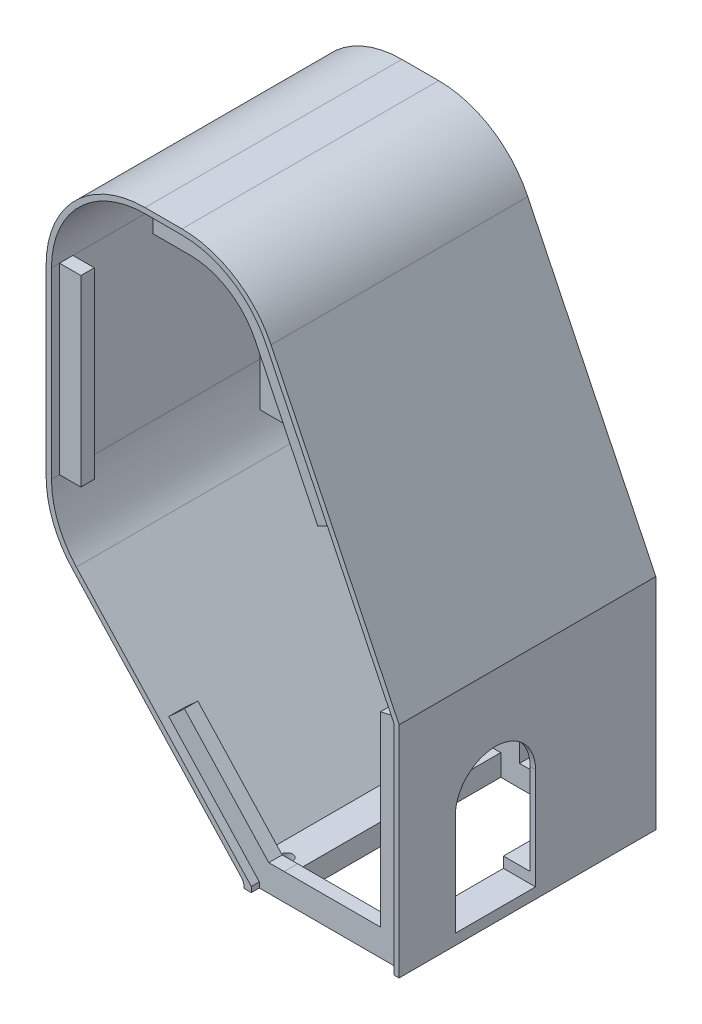
SolidWorks part; units mm, degrees
ref_plane "정면" through (0, 0, 0) normal (0, 0, 1) x (1, 0, 0)
ref_plane "윗면" through (0, 0, 0) normal (0, 1, 0) x (1, 0, 0)
ref_plane "우측면" through (0, 0, 0) normal (1, 0, 0) x (0, 0, -1)
sketch "스케치1" plane through (0, 0, 0) normal (0, 0, 1) x (1, 0, 0)
  line L0 (-65.9497, 38.7926) -> (-28.9497, -1.2074)
  line L1 (-28.9497, 98.7926) -> (-65.9497, 98.7926)
  line L2 (-65.9497, 38.7926) -> (-65.9497, 98.7926)
  line L4 (-28.9497, 98.7926) -> (0.0503, 38.7926)
  line L5 (0.0503, 38.7926) -> (0.0503, -1.2074)
  line L9 (-28.9497, -1.2074) -> (-28.9497, -2.2074)
  line L10 (-28.9497, -2.2074) -> (0.0503, -2.2074)
  line L11 (0.0503, -1.2074) -> (0.0503, -2.2074)
  line L12 (-28.9497, -1.2074) -> (0.0503, -2.2074) construction
  line L13 (-28.9497, -2.2074) -> (0.0503, -1.2074) construction
  point P10 (-14.4497, -1.7074)
  dimension "D1" = 37
  dimension "D2" = 29
  dimension "D3" = 40
  dimension "D5" = 1
extrude "보스-돌출1" add sketch "스케치1" against normal blind 6
fillet "필렛1" radius 18.5 3 edges at (-28.9497, 98.7926, -3) (-65.9497, 98.7926, -3) (-65.9497, 38.7926, -3)
sketch "스케치3" plane through (0, 0, -6) normal (0, 0, -1) x (-1, 0, 0)
  circle A0 centre (47.4497, 80.2926) radius 16.15
  dimension "D1" = 32.3
extrude "컷-돌출1" cut sketch "스케치3" against normal blind 4.5
sketch "스케치4" plane through (0, 0, -1.5) normal (0, 0, -1) x (-1, 0, 0)
  circle A0 centre (47.4497, 80.2926) radius 14.85
  circle A1 centre (47.4497, 80.2926) radius 16.15 construction
  dimension "D1" = 1.3
extrude "컷-돌출2" cut sketch "스케치4" against normal up to next
chamfer "모따기1" distance 1 angle 67 1 edges at (-63.5997, 80.2926, -6)
sketch "스케치5" plane through (0, 0, 0) normal (0, 0, 1) x (1, 0, 0)
  line L1 (-61.4497, 47.2926) -> (-33.4497, 47.2926)
  line L2 (-61.4497, 47.2926) -> (-61.4497, 41.2926)
  line L3 (-61.4497, 41.2926) -> (-33.4497, 41.2926)
  line L4 (-33.4497, 47.2926) -> (-33.4497, 41.2926)
  line L5 (-61.4497, 47.2926) -> (-33.4497, 41.2926) construction
  line L6 (-61.4497, 41.2926) -> (-33.4497, 47.2926) construction
  line L7 (-61.4497, 67.2926) -> (-58.4041, 67.2926)
  line L8 (-61.4497, 67.2926) -> (-61.4497, 57.2926)
  line L9 (-61.4497, 57.2926) -> (-54.5997, 57.2926)
  line L10 (-54.5997, 64.8693) -> (-54.5997, 57.2926)
  line L11 (-61.4497, 67.2926) -> (-54.5997, 57.2926) construction
  line L13 (-33.4497, 67.2926) -> (-36.4952, 67.2926)
  line L14 (-33.4497, 67.2926) -> (-33.4497, 57.2926)
  line L15 (-33.4497, 57.2926) -> (-40.2997, 57.2926)
  line L16 (-40.2997, 64.8693) -> (-40.2997, 57.2926)
  line L17 (-33.4497, 67.2926) -> (-40.2997, 57.2926) construction
  circle A0 centre (-47.4497, 80.2926) radius 14.85 construction
  arc A1 (-58.4041, 67.2926) -> (-54.5997, 64.8693) centre (-47.4497, 80.2926) ccw
  arc A2 (-40.2997, 64.8693) -> (-36.4952, 67.2926) centre (-47.4497, 80.2926) ccw
  point P4 (-47.4497, 44.2926)
  dimension "D3" = 33
  dimension "D6" = 14
  dimension "D9" = 34
  dimension "D1" = 6
  dimension "D2" = 10
  dimension "D4" = 10
  dimension "D5" = 10
  dimension "D7" = 28
  dimension "D8" = 14.3
extrude "보스-돌출2" add sketch "스케치5" along normal blind 6.5
sketch "스케치6" plane through (0, 0, 6.5) normal (0, 0, 1) x (1, 0, 0)
  line L0 (-33.4497, 47.2926) -> (-61.4497, 47.2926) construction
  line L1 (-54.5997, 47.2926) -> (-40.2997, 47.2926)
  line L2 (-54.5997, 47.2926) -> (-54.5997, 44.4926)
  line L3 (-54.5997, 44.4926) -> (-40.2997, 44.4926)
  line L4 (-40.2997, 47.2926) -> (-40.2997, 44.4926)
  line L5 (-54.5997, 47.2926) -> (-40.2997, 44.4926) construction
  line L6 (-54.5997, 44.4926) -> (-40.2997, 47.2926) construction
  line L7 (-61.4497, 41.2926) -> (-33.4497, 41.2926) construction
  point P4 (-47.4497, 45.8926)
  point P9 (-54.5997, 45.8926)
  point P10 (-47.4497, 41.2926)
  dimension "D1" = 3.2
  dimension "D2" = 14.3
  dimension "D3" = 7.15
extrude "컷-돌출3" cut sketch "스케치6" against normal blind 1.5
sketch "스케치7" plane through (0, 47.2926, 0) normal (0, 1, 0) x (1, 0, 0)
  line L0 (-54.5997, -5) -> (-54.5997, -6.5) construction
  line L1 (-61.4497, -6.5) -> (-54.5997, -6.5)
  line L2 (-61.4497, -6.5) -> (-61.4497, -3.5)
  line L3 (-61.4497, -3.5) -> (-54.5997, -3.5)
  line L4 (-54.5997, -6.5) -> (-54.5997, -3.5)
  line L5 (-61.4497, -6.5) -> (-54.5997, -3.5) construction
  line L6 (-61.4497, -3.5) -> (-54.5997, -6.5) construction
  line L7 (-33.4497, -6.5) -> (-40.2997, -6.5)
  line L8 (-33.4497, -6.5) -> (-33.4497, -3.8442)
  line L9 (-33.4497, -3.8442) -> (-40.2997, -3.8442)
  line L10 (-40.2997, -6.5) -> (-40.2997, -3.8442)
  line L11 (-33.4497, -6.5) -> (-40.2997, -3.8442) construction
  line L12 (-33.4497, -3.8442) -> (-40.2997, -6.5) construction
  line L14 (-40.2997, -5) -> (-40.2997, -6.5) construction
  point P4 (-58.0247, -5)
  point P10 (-36.8747, -5.1721)
  dimension "D1" = 3
extrude "보스-돌출3" add sketch "스케치7" along normal blind 28
sketch "스케치8" plane through (0, 0, 6.5) normal (0, 0, 1) x (1, 0, 0)
  line L0 (-54.5997, 44.4926) -> (-40.2997, 44.4926) construction
  line L1 (-57.6997, 71.7926) -> (-37.1997, 71.7926) construction
  line L2 (-57.6997, 71.7926) -> (-57.6997, 51.2926) construction
  line L3 (-57.6997, 51.2926) -> (-37.1997, 51.2926) construction
  line L4 (-37.1997, 71.7926) -> (-37.1997, 51.2926) construction
  line L5 (-57.6997, 71.7926) -> (-37.1997, 51.2926) construction
  line L6 (-57.6997, 51.2926) -> (-37.1997, 71.7926) construction
  circle A0 centre (-57.6997, 71.7926) radius 1.15
  circle A1 centre (-37.1997, 71.7926) radius 1.15
  circle A2 centre (-37.1997, 51.2926) radius 1.15
  circle A3 centre (-57.6997, 51.2926) radius 1.15
  circle A4 centre (-47.4497, 80.2926) radius 14.85 construction
  point P4 (-47.4497, 61.5426)
  dimension "D1" = 2.3
  dimension "D4" = 10.25
  dimension "D2" = 20.5
  dimension "D3" = 6.8
extrude "컷-돌출4" cut sketch "스케치8" against normal up to next
sketch "스케치9" plane through (0, 0, -6) normal (0, 0, -1) x (-1, 0, 0)
  circle A0 centre (57.6997, 51.2926) radius 2.1
  circle A1 centre (37.1997, 51.2926) radius 2.1
  dimension "D1" = 4.2
extrude "컷-돌출5" cut sketch "스케치9" against normal up to next
sketch "스케치10" plane through (0, 0, 6.5) normal (0, 0, 1) x (1, 0, 0)
  circle A0 centre (-47.4497, 80.2926) radius 10.75
  dimension "D1" = 21.5
extrude "컷-돌출6" cut sketch "스케치10" against normal up to next
sketch "스케치11" plane through (0, 0, -6) normal (0, 0, -1) x (-1, 0, 0)
  line L0 (26.9497, -2.2074) -> (26.9497, 36.7926) construction
  line L1 (28.9497, -2.2074) -> (-0.0503, -2.2074) construction
  line L2 (26.9497, 36.7926) -> (9.9497, 36.7926) construction
  line L3 (-0.0503, -2.2074) -> (-0.0503, 38.7926) construction
  line L4 (28.9497, -1.2074) -> (28.9497, -2.2074) construction
  line L5 (26.9497, 36.7926) -> (54.9497, 36.7926) construction
  circle A0 centre (9.9497, 36.7926) radius 1.4
  circle A1 centre (26.9497, 26.7926) radius 1.4
  circle A2 centre (26.9497, 6.7926) radius 1.4
  circle A3 centre (54.9497, 36.7926) radius 1.4
  dimension "D1" = 2.8
  dimension "D2" = 20
  dimension "D3" = 10
  dimension "D4" = 10
  dimension "D7" = 45
  dimension "D5" = 2
  dimension "D6" = 2
extrude "컷-돌출7" cut sketch "스케치11" against normal up to next
sketch "스케치12" plane through (0, 0, 0) normal (0, 0, 1) x (1, 0, 0)
  line L22 (0.0503, -2.2074) -> (0.0503, 38.7926) construction
  line L26 (-0.9497, -2.2074) -> (-0.9497, 38.5636)
  line L27 (-60.2964, 34.1536) -> (-28.2156, -0.5284)
  line L28 (-64.9497, 80.2926) -> (-64.9497, 46.0368)
  line L29 (-40.5556, 97.7926) -> (-47.4497, 97.7926)
  line L30 (-0.9497, 38.5636) -> (-24.7995, 87.908)
  line L31 (-0.9497, -2.2074) -> (-0.9497, 38.5636)
  line L32 (-60.2964, 34.1536) -> (-27.5875, -1.2074)
  line L33 (-64.9497, 80.2926) -> (-64.9497, 46.0368)
  line L34 (-40.5556, 97.7926) -> (-47.4497, 97.7926)
  line L35 (-0.9497, 38.5636) -> (-24.7995, 87.908)
  line L59 (-27.5875, -1.2074) -> (-27.5875, -2.2074)
  line L61 (-28.9497, -1.2074) -> (-28.9497, -2.2074)
  line L62 (-28.9497, -2.2074) -> (-27.5875, -2.2074)
  line L63 (-40.5556, 98.7926) -> (-47.4497, 98.7926)
  line L64 (0.0503, -2.2074) -> (0.0503, 38.7926)
  line L65 (0.0503, 38.7926) -> (-23.8992, 88.3432)
  line L66 (-61.0305, 33.4746) -> (-28.9497, -1.2074)
  line L67 (-65.9497, 80.2926) -> (-65.9497, 46.0368)
  line L68 (-40.5556, 98.7926) -> (-47.4497, 98.7926)
  line L69 (0.0503, -1.2074) -> (0.0503, 38.7926)
  line L70 (0.0503, 38.7926) -> (-23.8992, 88.3432)
  line L71 (-61.0305, 33.4746) -> (-28.9497, -1.2074)
  line L72 (-65.9497, 80.2926) -> (-65.9497, 46.0368)
  line L73 (0.0503, -1.2074) -> (0.0503, -2.2074)
  line L74 (-28.9497, -1.2074) -> (0.0503, -2.2074) construction
  line L75 (-28.9497, -2.2074) -> (0.0503, -1.2074) construction
  line L77 (-0.9497, -2.2074) -> (0.0503, -2.2074)
  arc A18 (-64.9497, 46.0368) -> (-60.2964, 34.1536) centre (-47.4497, 46.0368) ccw
  arc A19 (-47.4497, 97.7926) -> (-64.9497, 80.2926) centre (-47.4497, 80.2926) ccw
  arc A20 (-24.7995, 87.908) -> (-40.5556, 97.7926) centre (-40.5556, 80.2926) ccw
  arc A21 (-64.9497, 46.0368) -> (-60.2964, 34.1536) centre (-47.4497, 46.0368) ccw
  arc A22 (-47.4497, 97.7926) -> (-64.9497, 80.2926) centre (-47.4497, 80.2926) ccw
  arc A23 (-24.7995, 87.908) -> (-40.5556, 97.7926) centre (-40.5556, 80.2926) ccw
  arc A41 (-23.8992, 88.3432) -> (-40.5556, 98.7926) centre (-40.5556, 80.2926) ccw
  arc A42 (-65.9497, 46.0368) -> (-61.0305, 33.4746) centre (-47.4497, 46.0368) ccw
  arc A43 (-47.4497, 98.7926) -> (-65.9497, 80.2926) centre (-47.4497, 80.2926) ccw
  arc A44 (-23.8992, 88.3432) -> (-40.5556, 98.7926) centre (-40.5556, 80.2926) ccw
  arc A45 (-65.9497, 46.0368) -> (-61.0305, 33.4746) centre (-47.4497, 46.0368) ccw
  arc A46 (-47.4497, 98.7926) -> (-65.9497, 80.2926) centre (-47.4497, 80.2926) ccw
  point P8 (-14.4497, -1.7074)
  dimension "D1" = 1
  dimension "D2" = 0
extrude "보스-돌출4" add sketch "스케치12" along normal blind 42
sketch "스케치13" plane through (0, -2.2074, 0) normal (0, -1, 0) x (1, 0, 0)
  line L0 (-28.9497, -3) -> (0.0503, -3) construction
  line L2 (-28.9497, -6) -> (-28.9497, 42) construction
  line L3 (-28.9497, -6) -> (0.0503, -6) construction
  line L4 (0.0503, -6) -> (0.0503, 42) construction
  circle A1 centre (-14.4497, -3) radius 1.1
  dimension "D1" = 14.5
  dimension "D4" = 3
extrude "컷-돌출8" cut sketch "스케치13" against normal blind 8
sketch "스케치14" plane through (0, -2.2074, 0) normal (0, -1, 0) x (1, 0, 0)
  line L1 (-28.9497, -6) -> (-22.9497, -6)
  line L2 (-28.9497, -6) -> (-28.9497, 40)
  line L3 (-28.9497, 40) -> (-22.9497, 40)
  line L4 (-22.9497, -6) -> (-22.9497, 40)
  line L5 (-28.9497, -6) -> (-22.9497, 40) construction
  line L6 (-28.9497, 40) -> (-22.9497, -6) construction
  line L7 (-25.9497, 40) -> (-25.9497, -6) construction
  line L8 (-28.9497, -6) -> (0.0503, -6) construction
  line L9 (0.0503, 40) -> (-5.9497, 40)
  line L10 (0.0503, 40) -> (0.0503, -6)
  line L11 (0.0503, -6) -> (-5.9497, -6)
  line L12 (-5.9497, 40) -> (-5.9497, -6)
  line L13 (0.0503, 40) -> (-5.9497, -6) construction
  line L14 (0.0503, -6) -> (-5.9497, 40) construction
  line L15 (-2.9497, 40) -> (-2.9497, -6) construction
  line L17 (-24.7995, 42) -> (-0.9497, 42) construction
  line L18 (0.0503, -6) -> (0.0503, 42) construction
  circle A0 centre (-25.9497, 37) radius 1.1
  circle A1 centre (-25.9497, 12) radius 1.1
  circle A2 centre (-2.9497, 37) radius 1.1
  circle A3 centre (-2.9497, 12) radius 1.1
  point P4 (-25.9497, 17)
  point P18 (-2.9497, 17)
  dimension "D2" = 2.2
  dimension "D3" = 25
  dimension "D4" = 5
  dimension "D1" = 6
  dimension "D5" = 6
  dimension "D6" = 2
extrude "보스-돌출5" add sketch "스케치14" against normal blind 4
fillet "필렛2" radius 2 1 edges at (-28.9497, -1.2074, 18)
sketch "스케치15" plane through (0.0503, 0, 0) normal (1, 0, 0) x (0, 0, -1)
  line L0 (-42, -2.2074) -> (-42, 38.7926) construction
  line L1 (6, -2.2074) -> (-42, -2.2074) construction
  line L2 (-16.5, 18.7926) -> (-16.5, -0.2074)
  line L3 (-16.5, -0.2074) -> (-31.5, -0.2074)
  line L4 (-31.5, -0.2074) -> (-31.5, 18.7926)
  arc A0 (-16.5, 18.7926) -> (-31.5, 18.7926) centre (-24, 18.7926) ccw
  dimension "D1" = 15
  dimension "D3" = 21
  dimension "D2" = 18
  dimension "D4" = 2
extrude "컷-돌출10" cut sketch "스케치15" against normal up to next
sketch "스케치16" plane through (0, 0, -6) normal (0, 0, -1) x (-1, 0, 0)
  line L0 (4.4497, 18.7926) -> (4.4497, 1.7926)
  line L1 (4.4497, 1.7926) -> (19.4497, 1.7926)
  line L2 (19.4497, 1.7926) -> (19.4497, 18.7926)
  line L3 (-0.0503, -2.2074) -> (-0.0503, 38.7926) construction
  line L4 (28.9497, -2.2074) -> (-0.0503, -2.2074) construction
  arc A0 (19.4497, 18.7926) -> (4.4497, 18.7926) centre (11.9497, 18.7926) ccw
  dimension "D1" = 12
  dimension "D3" = 15
  dimension "D4" = 21
  dimension "D2" = 4
extrude "컷-돌출11" cut sketch "스케치16" against normal up to next
sketch "스케치17" plane through (0, 0, 42) normal (0, 0, 1) x (1, 0, 0)
  line L124 (-5.9497, 2.7926) -> (-4.9497, 2.7926)
  line L125 (-22.9497, 2.7926) -> (-5.9497, 2.7926)
  line L126 (-25.8214, 2.7814) -> (-22.9497, 2.7926)
  line L127 (-4.9497, 2.7926) -> (-4.9497, 37.6476)
  line L128 (-57.36, 36.8698) -> (-25.8214, 2.7814)
  line L129 (-60.9497, 80.2926) -> (-60.9497, 46.0368)
  line L130 (-4.9497, 37.6476) -> (-28.4009, 86.1673)
  line L131 (-40.5556, 93.7926) -> (-47.4497, 93.7926)
  line L132 (-5.9497, 2.7926) -> (-4.9497, 2.7926)
  line L133 (-22.9497, 2.7926) -> (-5.9497, 2.7926)
  line L134 (-25.8214, 2.7814) -> (-22.9497, 2.7926)
  line L135 (-4.9497, 2.7926) -> (-4.9497, 37.6476)
  line L136 (-41.5907, 19.8256) -> (-25.8214, 2.7814)
  line L137 (-60.9497, 80.2926) -> (-60.9497, 46.0368)
  line L138 (-16.6753, 61.9075) -> (-28.4009, 86.1673)
  line L139 (-40.5556, 93.7926) -> (-47.4497, 93.7926)
  line L218 (-47.4497, 98.7926) -> (-47.4497, 93.7926)
  line L219 (-60.9497, 80.2926) -> (-65.9497, 80.2926)
  line L220 (-65.9497, 46.0368) -> (-60.9497, 46.0368)
  line L221 (-4.9497, 37.6476) -> (0.0503, 38.7926)
  line L222 (-41.5907, 19.8256) -> (-45.256, 16.421)
  line L223 (-16.6753, 61.9075) -> (-12.1736, 64.0833)
  line L229 (-0.9497, -2.2074) -> (0.0503, -2.2074)
  line L230 (-65.9497, 80.2926) -> (-65.9497, 46.0368)
  line L231 (-28.9497, -1.9906) -> (-28.9497, -2.2074)
  line L232 (-61.0305, 33.4746) -> (-29.4815, -0.6325)
  line L233 (-28.9497, -2.2074) -> (-27.5875, -2.2074)
  line L234 (-27.5875, -2.2074) -> (-22.9497, -2.2074)
  line L235 (-5.9497, -2.2074) -> (-0.9497, -2.2074)
  line L236 (-22.9497, -2.2074) -> (-5.9497, -2.2074)
  line L237 (0.0503, -2.2074) -> (0.0503, 38.7926)
  line L238 (0.0503, 38.7926) -> (-23.8992, 88.3432)
  line L239 (-40.5556, 98.7926) -> (-47.4497, 98.7926)
  line L240 (-0.9497, -2.2074) -> (0.0503, -2.2074)
  line L241 (-65.9497, 80.2926) -> (-65.9497, 46.0368)
  line L242 (-28.9497, -1.9906) -> (-28.9497, -2.2074)
  line L243 (-45.256, 16.421) -> (-29.4815, -0.6325)
  line L244 (-28.9497, -2.2074) -> (-27.5875, -2.2074)
  line L245 (-27.5875, -2.2074) -> (-22.9497, -2.2074)
  line L246 (-5.9497, -2.2074) -> (-0.9497, -2.2074)
  line L247 (-22.9497, -2.2074) -> (-5.9497, -2.2074)
  line L248 (0.0503, -2.2074) -> (0.0503, 38.7926)
  line L249 (-12.1736, 64.0833) -> (-23.8992, 88.3432)
  line L250 (-40.5556, 98.7926) -> (-47.4497, 98.7926)
  arc A61 (-60.9497, 46.0368) -> (-57.36, 36.8698) centre (-47.4497, 46.0368) ccw
  arc A62 (-28.4009, 86.1673) -> (-40.5556, 93.7926) centre (-40.5556, 80.2926) ccw
  arc A63 (-47.4497, 93.7926) -> (-60.9497, 80.2926) centre (-47.4497, 80.2926) ccw
  arc A65 (-28.4009, 86.1673) -> (-40.5556, 93.7926) centre (-40.5556, 80.2926) ccw
  arc A106 (-65.9497, 46.0368) -> (-61.0305, 33.4746) centre (-47.4497, 46.0368) ccw
  arc A107 (-28.9497, -1.9906) -> (-29.4815, -0.6325) centre (-30.9497, -1.9906) ccw
  arc A108 (-23.8992, 88.3432) -> (-40.5556, 98.7926) centre (-40.5556, 80.2926) ccw
  arc A109 (-47.4497, 98.7926) -> (-65.9497, 80.2926) centre (-47.4497, 80.2926) ccw
  arc A111 (-28.9497, -1.9906) -> (-29.4815, -0.6325) centre (-30.9497, -1.9906) ccw
  arc A112 (-23.8992, 88.3432) -> (-40.5556, 98.7926) centre (-40.5556, 80.2926) ccw
  dimension "D1" = 5
  dimension "D2" = 0
extrude "보스-돌출6" add sketch "스케치17" against normal blind 2.5 from offset 1.5
